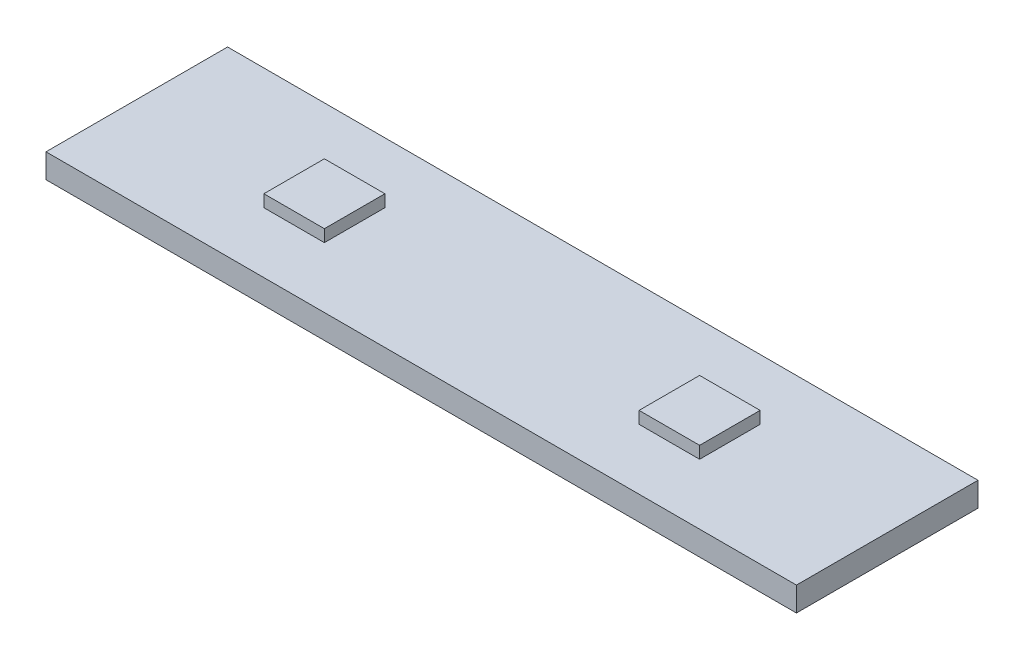
SolidWorks part; units mm, degrees
ref_plane "Front Plane" through (0, 0, 0) normal (0, 0, 1) x (1, 0, 0)
ref_plane "Top Plane" through (0, 0, 0) normal (0, 1, 0) x (1, 0, 0)
ref_plane "Right Plane" through (0, 0, 0) normal (1, 0, 0) x (0, 0, -1)
sketch "Sketch1" plane through (0, 0, 0) normal (0, 1, 0) x (1, 0, 0)
  line L1 (0, 0) -> (62, 0)
  line L2 (0, 0) -> (0, 15)
  line L3 (0, 15) -> (62, 15)
  line L4 (62, 0) -> (62, 15)
  dimension "D1" = 62
  dimension "D2" = 15
extrude "Boss-Extrude1" add sketch "Sketch1" along normal blind 2
sketch "Sketch2" plane through (0, 2, 0) normal (0, 1, 0) x (1, 0, 0)
  line L0 (31, 0) -> (31, 15) construction
  line L1 (13, 10) -> (18, 10)
  line L2 (13, 10) -> (13, 5)
  line L3 (13, 5) -> (18, 5)
  line L4 (18, 10) -> (18, 5)
  line L5 (0, 0) -> (62, 0) construction
  line L6 (62, 15) -> (0, 15) construction
  line L7 (15.5, 5) -> (15.5, 0) construction
  line L8 (15.5, 10) -> (15.5, 15) construction
  line L9 (49, 5) -> (44, 5)
  line L10 (44, 10) -> (44, 5)
  line L11 (49, 10) -> (44, 10)
  line L12 (49, 10) -> (49, 5)
  dimension "D1" = 5
  dimension "D2" = 13
extrude "Boss-Extrude2" add sketch "Sketch2" along normal blind 1
